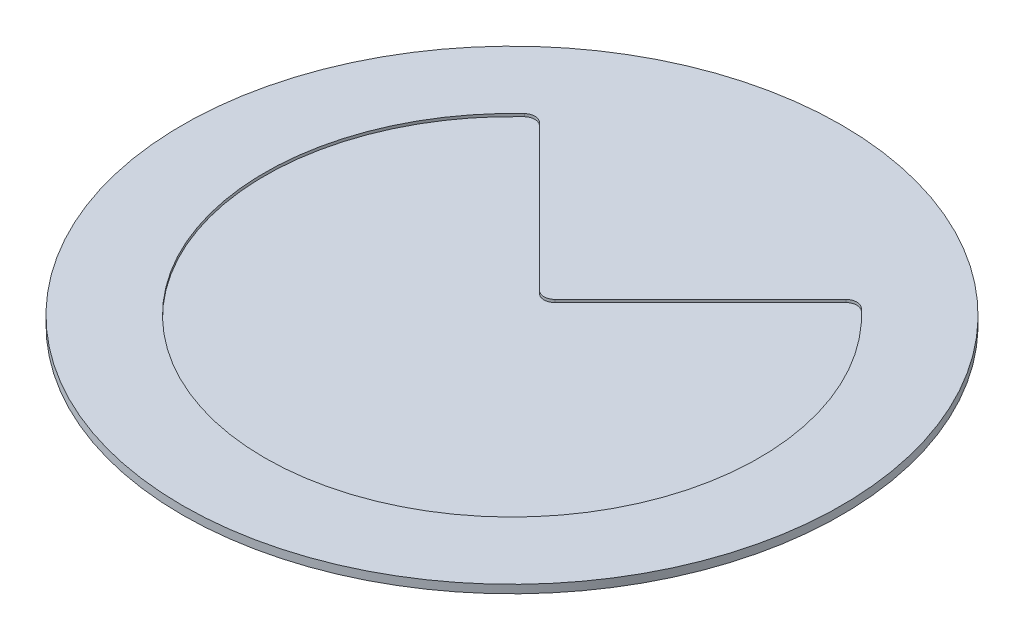
SolidWorks part; units mm, degrees
ref_plane "Front" through (0, 0, 0) normal (0, 0, 1) x (1, 0, 0)
ref_plane "Top" through (0, 0, 0) normal (0, 1, 0) x (1, 0, 0)
ref_plane "Right" through (0, 0, 0) normal (1, 0, 0) x (0, 0, -1)
sketch "Sketch1" plane through (0, 0, 0) normal (0, 1, 0) x (1, 0, 0)
  line L1 (0, 55.799) -> (0, -45) construction
  line L3 (-29.2214, 34.2214) -> (0, 5)
  line L4 (0, 5) -> (29.2214, 34.2214)
  line L5 (0, -50) -> (0, -56.3751) construction
  arc A2 (-29.2214, 34.2214) -> (29.2214, 34.2214) centre (0, 0) ccw
  circle A3 centre (0, 0) radius 60
  dimension "D1" = 120
  dimension "D3" = 90
  dimension "D4" = 90
  dimension "D5" = 5
extrude "Boss-Extrude1" add sketch "Sketch1" along normal blind 0.5
fillet "Fillet1" radius 2 3 edges at (-29.2214, 0.25, -34.2214) (29.2214, 0.25, -34.2214) (0, 0.25, -5)
sketch "Sketch2" plane through (0, 0, 0) normal (0, -1, 0) x (1, 0, 0)
  circle A0 centre (0, 0) radius 60
extrude "Boss-Extrude2" add sketch "Sketch2" along normal blind 1
